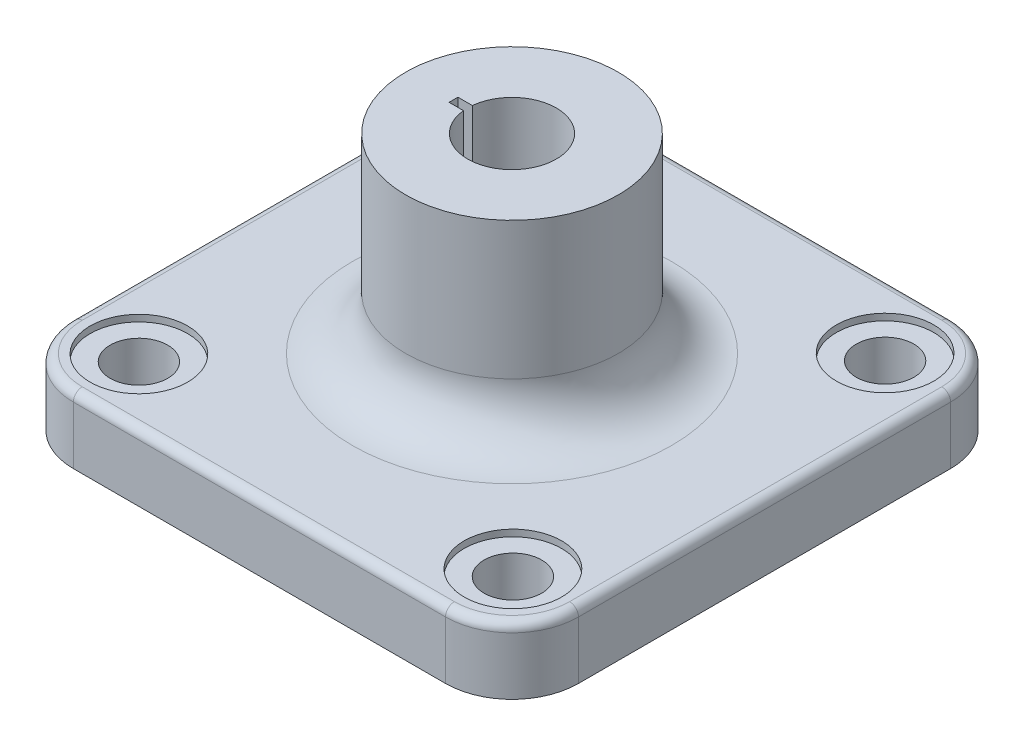
SolidWorks part; units mm, degrees
ref_plane "前基準面" through (0, 0, 0) normal (0, 0, 1) x (1, 0, 0)
ref_plane "上基準面" through (0, 0, 0) normal (0, 1, 0) x (1, 0, 0)
ref_plane "右基準面" through (0, 0, 0) normal (1, 0, 0) x (0, 0, -1)
sketch "草圖1" plane through (0, 0, 0) normal (0, 0, 1) x (1, 0, 0)
  line L0 (0, 0) -> (114, 0)
  line L1 (114, 0) -> (114, -15)
  line L2 (114, -15) -> (0, -15)
  line L3 (0, -15) -> (0, 0)
  dimension "D1" = 15
  dimension "D2" = 114
extrude "填料-伸長1" add sketch "草圖1" against normal blind 114
fillet "圓角3" radius 15 4 edges at (0, -7.5, -114) (0, -7.5, 0) (114, -7.5, -114) (114, -7.5, 0)
fillet "圓角4" radius 2 8 edges at (109.6066, 0, -4.3934) (114, 0, -57) (109.6066, 0, -109.6066) (57, 0, -114) (4.3934, 0, -109.6066) (0, 0, -57) (4.3934, 0, -4.3934) (57, 0, 0)
sketch "草圖2" plane through (0, 0, 0) normal (0, 1, 0) x (1, 0, 0)
  line L0 (57, 112) -> (57, 2) construction
  line L1 (99, 112) -> (15, 112) construction
  line L2 (57, 57) -> (118.3966, 57) construction
  line L3 (57, 57) -> (43.8, 57) construction
  line L4 (47.0501, 58) -> (43.8, 58)
  line L5 (47.0501, 56) -> (43.8, 56)
  line L6 (57, 58) -> (57, 56)
  line L7 (43.8, 58) -> (43.8, 56)
  line L8 (57, 58) -> (43.8, 58) construction
  line L9 (57, 56) -> (43.8, 56) construction
  line L10 (0, 57) -> (13.1977, 57) construction
  line L11 (0, 15) -> (0, 99) construction
  arc A0 (47.0501, 56) -> (47.0501, 58) centre (57, 57) ccw
  circle A1 centre (57, 57) radius 24
  dimension "D1" = 48
  dimension "D2" = 20
  dimension "D5" = 23.2
  dimension "D3" = 1
  dimension "D4" = 1
extrude "填料-伸長2" add sketch "草圖2" along normal blind 43 contours A1 A0 L5 L7 L4 region at (33.6788, 0, -57)
fillet "圓角5" radius 12 1 edges at (57, 0, -33)
sketch "草圖3" plane through (0, 0, 0) normal (0, 1, 0) x (1, 0, 0)
  line L0 (99, 112) -> (99, 86.4125) construction
  line L1 (112, 99) -> (87.2161, 99) construction
  circle A0 centre (99, 99.2063) radius 6.5
  circle A1 centre (99, 99.2063) radius 11
  dimension "D1" = 13
  dimension "D2" = 22
extrude "除料-伸長4" cut sketch "草圖3" against normal through all contours A0 region at (99, 0, -99.2063)
extrude "除料-伸長5" cut sketch "草圖3<4>" against normal blind 1.5
sketch "草圖3<4>" plane through (0, 0, 0) normal (0, 1, 0) x (1, 0, 0) same geometry as "草圖3"
pattern_circular "環狀複製排列1" count 4 over 360 about axis through (57, 43, -57) along (0, -1, 0) of "除料-伸長5", "除料-伸長4" reverse direction yes
sketch "草圖11" plane through (0, 0, 0) normal (0, 0, 1) x (1, 0, 0)
  line L0 (81, 43) -> (113.3894, -3.4386)
  line L1 (57, 12) -> (57, 126.9419) construction
  line L2 (81, 12) -> (33, 12) construction
  line L3 (115.7539, 12) -> (3.7945, 12) construction
  line L4 (113.3894, 28.5) -> (113.3894, -4.5) construction
  arc A0 (114, -2) -> (112, 0) centre (112, -2) ccw construction
  circle A1 centre (57, 12) radius 58.7539 construction
  dimension "D1" = 33
